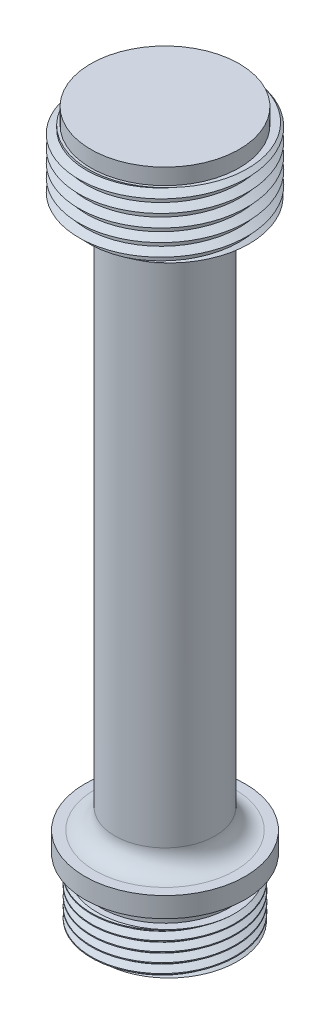
SolidWorks part; units mm, degrees
material "Aluminum 6061-T6 "
ref_plane "Front Plane" through (0, 0, 0) normal (0, 0, 1) x (1, 0, 0)
ref_plane "Top Plane" through (0, 0, 0) normal (0, 1, 0) x (1, 0, 0)
ref_plane "Right Plane" through (0, 0, 0) normal (1, 0, 0) x (0, 0, -1)
sketch "Sketch1" plane through (0, 0, 0) normal (0, 0, 1) x (1, 0, 0)
  line L0 (0, 0) -> (0, 33.1679) construction
  line L1 (0, 0) -> (11.75, 0)
  line L2 (11.75, 0) -> (11.75, -2.54)
  line L3 (11.75, -2.54) -> (13.481, -2.54)
  line L4 (13.481, -2.54) -> (13.481, -12.7)
  line L5 (13.481, -12.7) -> (7.9375, -12.7)
  line L6 (7.9375, -12.7) -> (7.9375, -99.187)
  line L7 (7.9375, -99.187) -> (12.7, -99.187)
  line L8 (12.7, -99.187) -> (12.7, -102.362)
  line L9 (12.7, -102.362) -> (10.16, -102.362)
  line L10 (10.16, -102.362) -> (10.16, -104.775)
  line L11 (10.16, -104.775) -> (11.4046, -104.775)
  line L12 (11.4046, -104.775) -> (11.4046, -111.887)
  line L13 (11.4046, -111.887) -> (0, -111.887)
  line L14 (0, -111.887) -> (0, 0)
  point P28 (5.7023, -111.887)
  dimension "D1" = 26.962
  dimension "D2" = 23.5
  dimension "D3" = 25.4
  dimension "D4" = 12.7
  dimension "D5" = 10.16
  dimension "D6" = 3.175
  dimension "D7" = 7.112
  dimension "D8" = 22.8092
  dimension "D9" = 9.525
  dimension "D10" = 15.875
  dimension "D11" = 20.32
  dimension "D12" = 102.362
revolve "Revolve1" add sketch "Sketch1" angle 360 about L0
sketch "Sketch2" plane through (0, 0, 0) normal (0, 1, 0) x (1, 0, 0)
  circle A0 centre (0, 0) radius 12.8315
  dimension "D1" = 25.663
sketch "Sketch3" plane through (0, 0, 0) normal (0, 0, 1) x (1, 0, 0)
  line L0 (12.1305, 0.3285) -> (14.1015, 1.4665)
  line L1 (14.1015, 1.4665) -> (14.1015, -1.4665)
  line L2 (14.1015, -1.4665) -> (12.1305, -0.3285)
  line L3 (12.1305, -0.3285) -> (12.1305, 0.3285)
  line L4 (12.1305, 0.3285) -> (11.5615, 0) construction
  line L5 (11.5615, 0) -> (12.1305, -0.3285) construction
  line L6 (11.5615, 0) -> (14.1015, 0) construction
  line L9 (0, 0) -> (0, -2.54) construction
  point P5 (12.8315, 0)
  dimension "D1" = 60
  dimension "D2" = 2.54
  dimension "D3" = 12.1305
curve "Helix/Spiral2" pitch 2 height 16 radius 12.8315 centre (0, 0, 0) axis (0, -1, 0) start towards (1, 0, 0)
sweep "M27 x 2mm Thread" cut profiles "Sketch3" path "Helix/Spiral2" align with end faces yes
ref_plane "Plane1" through (0, -114.427, 0) normal (0, -1, 0) x (-1, 0, 0)
sketch "Sketch5" plane through (0, -114.427, 0) normal (0, -1, 0) x (-1, 0, 0)
  circle A0 centre (0, 0) radius 10.8712
  dimension "D1" = 21.7424
curve "Helix/Spiral3" pitch 1.5 height 10.875 radius 10.8712 centre (0, -114.427, 0) axis (0, 1, 0) start towards (1, 0, 0)
sketch "Sketch6" plane through (0, 0, 0) normal (0, 0, 1) x (1, 0, 0)
  line L0 (10.3986, -114.3332) -> (11.5062, -113.6938)
  line L1 (11.5062, -113.6938) -> (11.5062, -115.1602)
  line L2 (11.5062, -115.1602) -> (10.3986, -114.5208)
  line L3 (10.3986, -114.5208) -> (10.3986, -114.3332)
  line L4 (10.3986, -114.5208) -> (10.2362, -114.427) construction
  line L5 (10.2362, -114.427) -> (10.3986, -114.3332) construction
  line L6 (10.2362, -114.427) -> (11.5062, -114.427) construction
  line L9 (0, -104.775) -> (0, -111.887) construction
  point P2 (10.8712, -114.427)
  dimension "D1" = 60
  dimension "D2" = 0.1624
  dimension "D3" = 1.27
  dimension "D4" = 10.3986
sweep "M23 x 1.5mm Thread" cut profiles "Sketch6" path "Helix/Spiral3" align with end faces yes
hole_wizard "3/8 (0.375) Diameter Hole1" positions "Sketch7" profile "Sketch8" hole size "3/8" standard "ANSI Inch"
sketch "Sketch7" plane through (0, -111.887, 0) normal (0, -1, 0) x (-1, 0, 0)
  point P0 (0, 0)
sketch "Sketch8" plane through (0, -111.887, 0) normal (1, 0, 0) x (0, 0, -1)
  line L0 (0, 0) -> (0, 110.0496)
  line L1 (0, 110.0496) -> (4.7625, 107.188)
  line L2 (4.7625, 107.188) -> (4.7625, 0)
  line L5 (4.7625, 0) -> (0, 0)
  line L10 (0, 110.0496) -> (-4.7625, 107.188) construction
  line L11 (0, -6.35) -> (0, 107.95) construction
  dimension "Hole Dia." = 9.525
  dimension "Hole Depth" = 107.188
  dimension "Drill Angle" = 118
hole_wizard "9/16 (0.5625) Diameter Hole1" positions "Sketch9" profile "Sketch10" hole size "9/16" standard "ANSI Inch"
sketch "Sketch9" plane through (0, -111.887, 0) normal (0, -1, 0) x (-1, 0, 0)
  point P0 (0, 0)
sketch "Sketch10" plane through (0, -111.887, 0) normal (1, 0, 0) x (0, 0, -1)
  line L0 (0, 0) -> (0, 13.8174)
  line L1 (0, 13.8174) -> (7.1437, 9.525)
  line L2 (7.1437, 9.525) -> (7.1437, 0)
  line L5 (7.1437, 0) -> (0, 0)
  line L10 (0, 13.8174) -> (-7.1437, 9.525) construction
  line L11 (0, -6.35) -> (0, 107.95) construction
  dimension "Hole Dia." = 14.2875
  dimension "Hole Depth" = 9.525
  dimension "Drill Angle" = 118
fillet "Fillet1" radius 3.175 2 edges at (0, -99.187, -7.9375) (0, -12.7, -7.9375)
